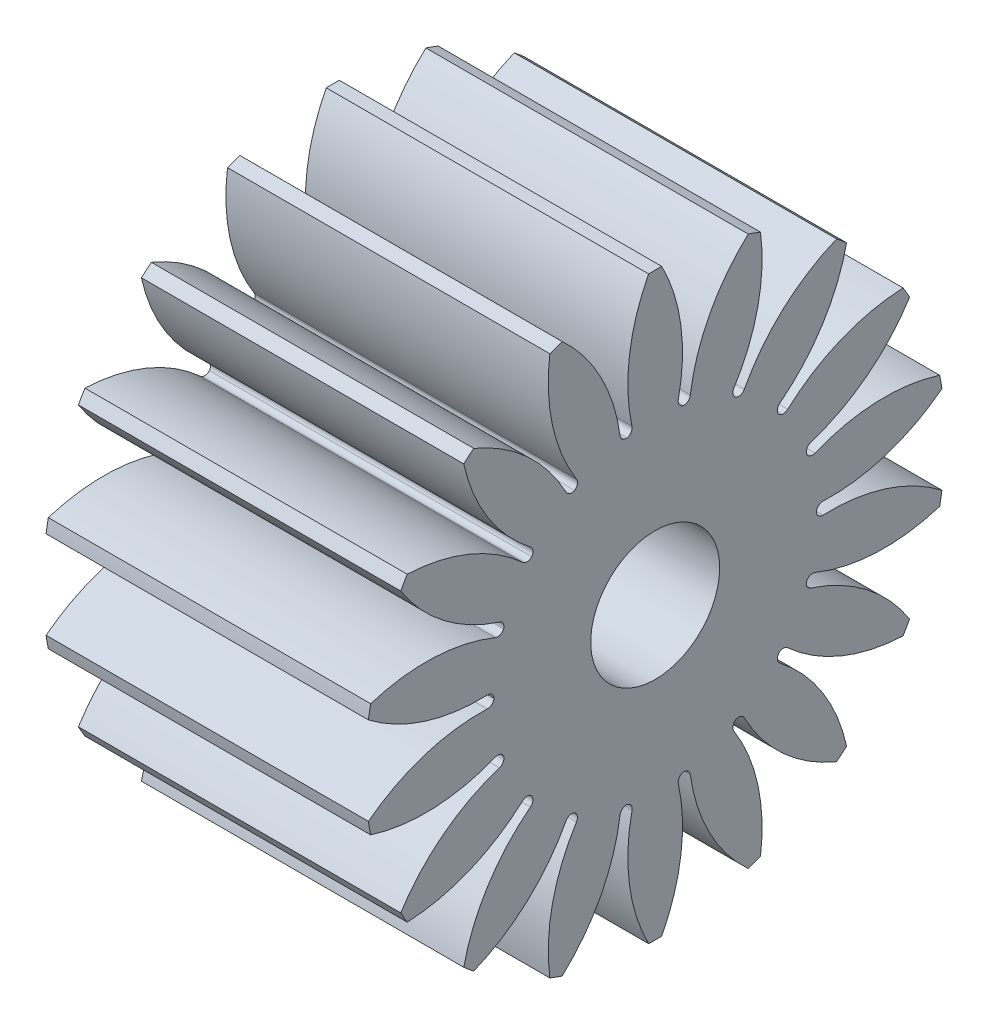
SolidWorks part; units mm, degrees
ref_plane "Front Plane" through (0, 0, 0) normal (1, 0, 0) x (0, 1, 0)
ref_plane "Top Plane" through (0, 0, 0) normal (0, 0, 1) x (0, 1, 0)
ref_plane "Right Plane" through (0, 0, 0) normal (0, 1, 0) x (-1, 0, 0)
sketch "Sketch1" plane through (0, 0, 0) normal (1, 0, 0) x (0, 1, 0)
  circle A0 centre (0, 0) radius 45
  dimension "D1" = 90
extrude "Boss-Extrude1" add sketch "Sketch1" along normal blind 50
sketch "Sketch2" plane through (50, 0, 0) normal (1, 0, 0) x (0, 1, 0)
  line L0 (0, 25) -> (0, 45) construction
  line L1 (8.5505, 23.4923) -> (15.3909, 42.2862) construction
  arc A0 (8.8102, 44.1291) -> (6.8142, 44.4811) centre (0, 0) ccw
  arc A2 (1, 24.98) -> (-1, 24.98) centre (0, 0) ccw
  arc A3 (1, 24.98) -> (6.8142, 44.4811) centre (29.3908, 27.1327) cw
  arc A5 (9.4834, 23.1315) -> (21.6167, 39.468) centre (36.8982, 15.4442) cw
  arc A6 (7.604, 23.8155) -> (8.8102, 44.1291) centre (-18.3384, 35.5486) ccw
  arc A7 (15.2908, 19.7786) -> (23.3719, 38.4546) centre (-5.0741, 39.6769) ccw
  arc A8 (23.3719, 38.4546) -> (21.6167, 39.468) centre (0, 0) ccw
  arc A9 (16.8229, 18.493) -> (33.8118, 29.6944) centre (39.9552, 1.8928) cw
  arc A10 (21.1333, 13.356) -> (35.1147, 28.1418) centre (8.8022, 39.0195) ccw
  arc A11 (35.1147, 28.1418) -> (33.8118, 29.6944) centre (0, 0) ccw
  arc A12 (22.1333, 11.624) -> (41.9288, 16.3393) centre (38.193, -11.8868) cw
  arc A13 (24.4268, 5.3225) -> (42.6221, 14.4347) centre (21.6168, 33.6558) ccw
  arc A14 (42.6221, 14.4347) -> (41.9288, 16.3393) centre (0, 0) ccw
  arc A15 (24.7741, 3.3529) -> (44.9886, 1.0134) centre (31.8241, -24.2327) cw
  arc A16 (24.7741, -3.3529) -> (44.9886, -1.0134) centre (31.8241, 24.2327) ccw
  arc A17 (44.9886, -1.0134) -> (44.9886, 1.0134) centre (0, 0) ccw
  arc A18 (24.4268, -5.3225) -> (42.6221, -14.4347) centre (21.6168, -33.6558) cw
  arc A19 (22.1333, -11.624) -> (41.9288, -16.3393) centre (38.193, 11.8868) ccw
  arc A20 (41.9288, -16.3393) -> (42.6221, -14.4347) centre (0, 0) ccw
  arc A21 (21.1333, -13.356) -> (35.1147, -28.1418) centre (8.8022, -39.0195) cw
  arc A22 (16.8229, -18.493) -> (33.8118, -29.6944) centre (39.9552, -1.8928) ccw
  arc A23 (33.8118, -29.6944) -> (35.1147, -28.1418) centre (0, 0) ccw
  arc A24 (15.2908, -19.7786) -> (23.3719, -38.4546) centre (-5.0741, -39.6769) cw
  arc A25 (9.4834, -23.1315) -> (21.6167, -39.468) centre (36.8982, -15.4442) ccw
  arc A26 (21.6167, -39.468) -> (23.3719, -38.4546) centre (0, 0) ccw
  arc A27 (7.604, -23.8155) -> (8.8102, -44.1291) centre (-18.3384, -35.5486) cw
  arc A28 (1, -24.98) -> (6.8142, -44.4811) centre (29.3908, -27.1327) ccw
  arc A29 (6.8142, -44.4811) -> (8.8102, -44.1291) centre (0, 0) ccw
  arc A30 (-1, -24.98) -> (-6.8142, -44.4811) centre (-29.3908, -27.1327) cw
  arc A31 (-7.604, -23.8155) -> (-8.8102, -44.1291) centre (18.3384, -35.5486) ccw
  arc A32 (-8.8102, -44.1291) -> (-6.8142, -44.4811) centre (0, 0) ccw
  arc A33 (-9.4834, -23.1315) -> (-21.6167, -39.468) centre (-36.8982, -15.4442) cw
  arc A34 (-15.2908, -19.7786) -> (-23.3719, -38.4546) centre (5.0741, -39.6769) ccw
  arc A35 (-23.3719, -38.4546) -> (-21.6167, -39.468) centre (0, 0) ccw
  arc A36 (-16.8229, -18.493) -> (-33.8118, -29.6944) centre (-39.9552, -1.8928) cw
  arc A37 (-21.1333, -13.356) -> (-35.1147, -28.1418) centre (-8.8022, -39.0195) ccw
  arc A38 (-35.1147, -28.1418) -> (-33.8118, -29.6944) centre (0, 0) ccw
  arc A39 (-22.1333, -11.624) -> (-41.9288, -16.3393) centre (-38.193, 11.8868) cw
  arc A40 (-24.4268, -5.3225) -> (-42.6221, -14.4347) centre (-21.6168, -33.6558) ccw
  arc A41 (-42.6221, -14.4347) -> (-41.9288, -16.3393) centre (0, 0) ccw
  arc A42 (-24.7741, -3.3529) -> (-44.9886, -1.0134) centre (-31.8241, 24.2327) cw
  arc A43 (-24.7741, 3.3529) -> (-44.9886, 1.0134) centre (-31.8241, -24.2327) ccw
  arc A44 (-44.9886, 1.0134) -> (-44.9886, -1.0134) centre (0, 0) ccw
  arc A45 (-24.4268, 5.3225) -> (-42.6221, 14.4347) centre (-21.6168, 33.6558) cw
  arc A46 (-22.1333, 11.624) -> (-41.9288, 16.3393) centre (-38.193, -11.8868) ccw
  arc A47 (-41.9288, 16.3393) -> (-42.6221, 14.4347) centre (0, 0) ccw
  arc A48 (-21.1333, 13.356) -> (-35.1147, 28.1418) centre (-8.8022, 39.0195) cw
  arc A49 (-16.8229, 18.493) -> (-33.8118, 29.6944) centre (-39.9552, 1.8928) ccw
  arc A50 (-33.8118, 29.6944) -> (-35.1147, 28.1418) centre (0, 0) ccw
  arc A51 (-15.2908, 19.7786) -> (-23.3719, 38.4546) centre (5.0741, 39.6769) cw
  arc A52 (-9.4834, 23.1315) -> (-21.6167, 39.468) centre (-36.8982, 15.4442) ccw
  arc A53 (-21.6167, 39.468) -> (-23.3719, 38.4546) centre (0, 0) ccw
  arc A54 (-7.604, 23.8155) -> (-8.8102, 44.1291) centre (18.3384, 35.5486) cw
  arc A55 (-1, 24.98) -> (-6.8142, 44.4811) centre (-29.3908, 27.1327) ccw
  arc A56 (-6.8142, 44.4811) -> (-8.8102, 44.1291) centre (0, 0) ccw
  arc A57 (-7.604, 23.8155) -> (-9.4834, 23.1315) centre (0, 0) ccw
  arc A58 (9.4834, 23.1315) -> (7.604, 23.8155) centre (0, 0) ccw
  arc A59 (16.8229, 18.493) -> (15.2908, 19.7786) centre (0, 0) ccw
  arc A60 (22.1333, 11.624) -> (21.1333, 13.356) centre (0, 0) ccw
  arc A61 (24.7741, 3.3529) -> (24.4268, 5.3225) centre (0, 0) ccw
  arc A62 (24.4268, -5.3225) -> (24.7741, -3.3529) centre (0, 0) ccw
  arc A63 (-15.2908, 19.7786) -> (-16.8229, 18.493) centre (0, 0) ccw
  arc A64 (-21.1333, 13.356) -> (-22.1333, 11.624) centre (0, 0) ccw
  arc A65 (-24.4268, 5.3225) -> (-24.7741, 3.3529) centre (0, 0) ccw
  arc A66 (-24.7741, -3.3529) -> (-24.4268, -5.3225) centre (0, 0) ccw
  arc A67 (-22.1333, -11.624) -> (-21.1333, -13.356) centre (0, 0) ccw
  arc A68 (-16.8229, -18.493) -> (-15.2908, -19.7786) centre (0, 0) ccw
  arc A69 (-9.4834, -23.1315) -> (-7.604, -23.8155) centre (0, 0) ccw
  arc A70 (-1, -24.98) -> (1, -24.98) centre (0, 0) ccw
  arc A71 (7.604, -23.8155) -> (9.4834, -23.1315) centre (0, 0) ccw
  arc A72 (15.2908, -19.7786) -> (16.8229, -18.493) centre (0, 0) ccw
  arc A73 (21.1333, -13.356) -> (22.1333, -11.624) centre (0, 0) ccw
  point P114 (0, 0)
  dimension "D1" = 18
  dimension "D2" = 50
  dimension "D6" = 90
  dimension "D3" = 20
extrude "Cut-Extrude1" cut sketch "Sketch2" against normal through all both and the other way through all flip side to cut
fillet "Fillet4" radius 1 2 edges at (25, 9.4834, 23.1315) (25, 7.604, 23.8155)
fillet "Fillet5" radius 1 34 edges at (25, -1, 24.98) (25, -9.4834, 23.1315) (25, -15.2908, 19.7786) (25, -21.1333, 13.356) (25, 1, 24.98) (25, -7.604, 23.8155) (25, -16.8229, 18.493) (25, -22.1333, 11.624) (25, -24.7741, 3.3529) (25, -24.4268, 5.3225) (25, -24.7741, -3.3529) (25, -24.4268, -5.3225) (25, -21.1333, -13.356) (25, -22.1333, -11.624) (25, -15.2908, -19.7786) (25, -7.604, -23.8155) (25, -16.8229, -18.493) (25, -9.4834, -23.1315) (25, -1, -24.98) (25, 1, -24.98) (25, 7.604, -23.8155) (25, 9.4834, -23.1315) (25, 15.2908, -19.7786) (25, 16.8229, -18.493) (25, 21.1333, -13.356) (25, 22.1333, -11.624) (25, 24.4268, -5.3225) (25, 24.7741, -3.3529) (25, 24.7741, 3.3529) (25, 24.4268, 5.3225) (25, 21.1333, 13.356) (25, 22.1333, 11.624) (25, 16.8229, 18.493) (25, 15.2908, 19.7786)
sketch "Sketch3" plane through (50, 0, 0) normal (1, 0, 0) x (0, 0, -1)
  circle A0 centre (0, 0) radius 10
  dimension "D1" = 20
extrude "Cut-Extrude2" cut sketch "Sketch3" against normal through all both and the other way through all
